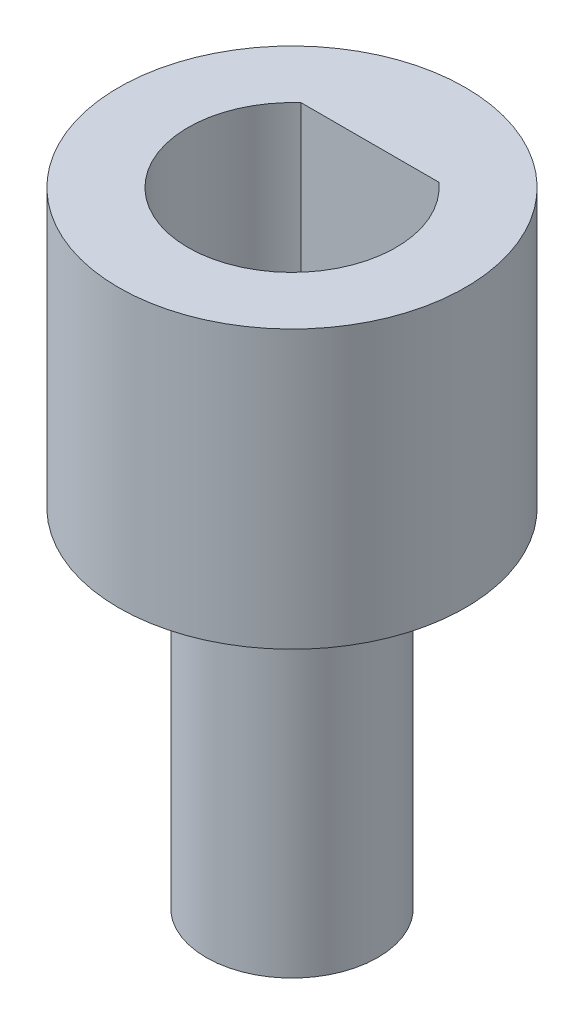
SolidWorks part; units mm, degrees
ref_plane "Front Plane" through (0, 0, 0) normal (0, 0, 1) x (1, 0, 0)
ref_plane "Top Plane" through (0, 0, 0) normal (0, 1, 0) x (1, 0, 0)
ref_plane "Right Plane" through (0, 0, 0) normal (1, 0, 0) x (0, 0, -1)
sketch "Sketch1" plane through (0, 0, 0) normal (0, 1, 0) x (1, 0, 0)
  circle A1 centre (0, 0) radius 2.475
  circle A2 centre (0, 0) radius 1.5
  dimension "D1" = 4.95
  dimension "D2" = 3
extrude "Boss-Extrude1" add sketch "Sketch1" along normal blind 5
extrude "Boss-Extrude2" add sketch "Sketch1<2>" along normal blind 5 from surface contours A1 A2 | A2 region at (-2.405, 0, 0) region at (0, 0, 0) starting at face at (0, 5, 2.475)
sketch "Sketch1<2>" plane through (0, 0, 0) normal (0, 1, 0) x (1, 0, 0) same geometry as "Sketch1"
sketch "Sketch2" plane through (0, 10, 0) normal (0, 1, 0) x (1, 0, 0)
  line L0 (-1.9843, 2.25) -> (1.9843, 2.25)
  arc A0 (-1.9843, 2.25) -> (1.9843, 2.25) centre (0, 0) ccw
  circle A1 centre (0, 0) radius 5
  circle M4 centre (0, 0) radius 2.475
  dimension "D1" = 6
  dimension "D2" = 10
  dimension "D3" = 2.25
extrude "Boss-Extrude3" add sketch "Sketch2" along normal blind 1 contours L0 A0 M4 | A1 A0 L0 M4 | L0 M4 | L0 M4 region at (-1.5077, 10, -2.1703) region at (0, 10, -2.3404) region at (0, 10, 0.0386) region at (-4.8586, 10, 0)
extrude "Boss-Extrude4" add sketch "Sketch2<3>" along normal blind 7 from surface starting at face at (0, 11, 5)
sketch "Sketch2<3>" plane through (0, 10, 0) normal (0, 1, 0) x (1, 0, 0) same geometry as "Sketch2"
fillet "Fillet1" radius 0.5 3 edges at (0, 10, 2.475) (0, 11, 3) (0, 11, -2.25)
